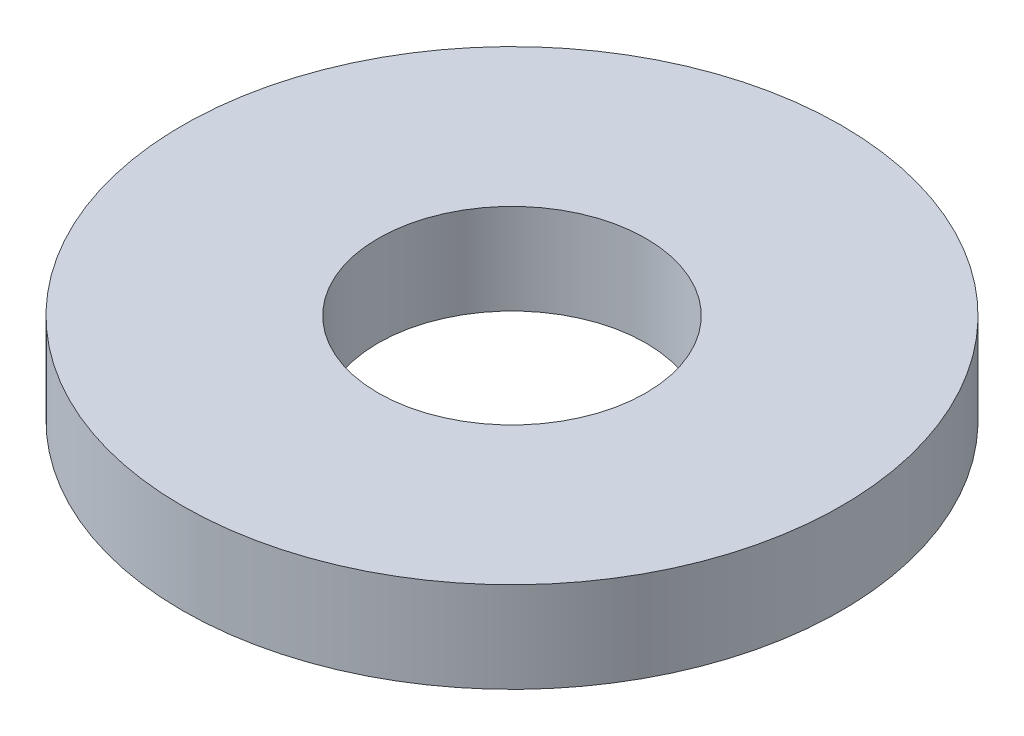
SolidWorks part; units mm, degrees
ref_plane "Front Plane" through (0, 0, 0) normal (0, 0, 1) x (1, 0, 0)
ref_plane "Top Plane" through (0, 0, 0) normal (0, 1, 0) x (1, 0, 0)
ref_plane "Right Plane" through (0, 0, 0) normal (1, 0, 0) x (0, 0, -1)
sketch "Sketch1" plane through (0, 0, 0) normal (0, 1, 0) x (1, 0, 0)
  circle A0 centre (0, 0) radius 80
  dimension "FLANGE_OD" = 160
extrude "Boss-Extrude1" add sketch "Sketch1" along normal blind 22
sketch "Sketch2" plane through (0, 0, 0) normal (0, 1, 0) x (1, 0, 0)
  circle A0 centre (0, 0) radius 32.5
  dimension "BORE_D" = 65
extrude "Cut-Extrude1" cut sketch "Sketch2" along normal through all
sketch "Sketch3" plane through (0, 22, 0) normal (0, 1, 0) x (1, 0, 0)
  circle A0 centre (0, 0) radius 21.2813 construction
  circle A1 centre (-21.2813, 0) radius 7.9265
  dimension "BOLT_D" = 15.853
  dimension "BOLT_PCD" = 42.5626
extrude "Cut-Extrude2" cut sketch "Sketch3" against normal blind 19.8573 rebuild error yes
pattern_circular "CirPattern1" count 6 over 360 rebuild error yes
